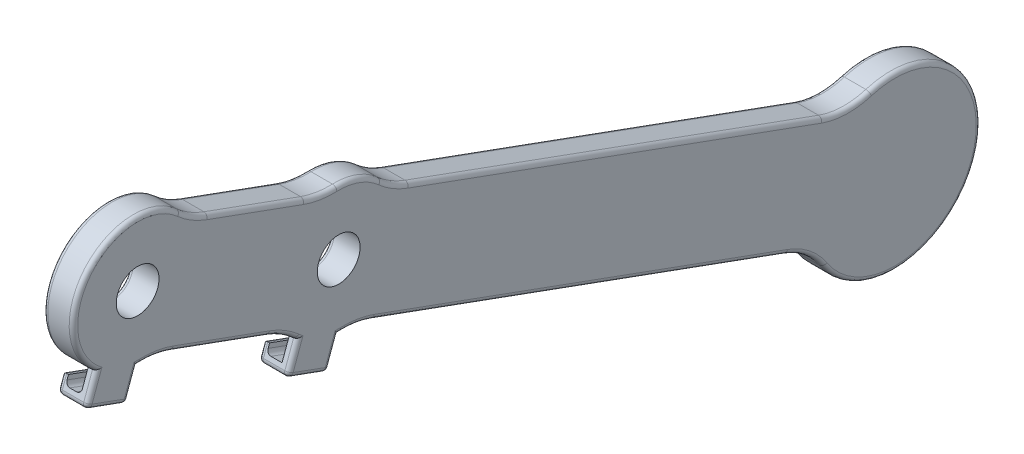
SolidWorks part; units mm, degrees
ref_plane "Front Plane" through (0, 0, 0) normal (1, 0, 0) x (0, 1, 0)
ref_plane "Top Plane" through (0, 0, 0) normal (0, 0, 1) x (0, 1, 0)
ref_plane "Right Plane" through (0, 0, 0) normal (0, 1, 0) x (-1, 0, 0)
sketch "Sketch1" plane through (0, 0, 0) normal (1, 0, 0) x (0, 1, 0)
  line L0 (-11.6048, -20) -> (24.9519, -20)
  line L1 (84.9519, 40) -> (84.9519, 57.8005)
  line L4 (-38.5328, 56.8878) -> (-47.7982, 43.6554)
  line L5 (64.9519, 37.5) -> (87.5414, -36.1119)
  line L6 (87.5414, -36.1119) -> (67.3498, -81.8536)
  line L7 (67.3498, -81.8536) -> (2.5345, -208.1983)
  line L8 (67.3498, -81.8536) -> (0, 0)
  line L9 (0, 0) -> (64.9519, 37.5) construction
  line L11 (-49.5322, 36.7009) -> (-46.3439, 10.7346)
  line L12 (-32.0778, 61.0001) -> (61.4789, 77.4967)
  arc A0 (24.9519, -20) -> (84.9519, 40) centre (24.9519, 40) ccw
  arc A1 (84.9519, 57.8005) -> (61.4789, 77.4967) centre (64.9519, 57.8005) ccw
  circle A3 centre (0, 0) radius 5
  circle A4 centre (0, 0) radius 10
  circle A5 centre (64.9519, 37.5) radius 5
  circle A6 centre (64.9519, 37.5) radius 10
  circle A7 centre (87.5414, -36.1119) radius 5
  circle A8 centre (87.5414, -36.1119) radius 10
  circle A9 centre (67.3498, -81.8536) radius 5
  circle A10 centre (67.3498, -81.8536) radius 10
  circle A11 centre (2.5345, -208.1983) radius 10
  circle A12 centre (2.5345, -208.1983) radius 50
  arc A13 (-46.3439, 10.7346) -> (-11.6048, -20) centre (-11.6048, 15) ccw
  arc A14 (-47.7982, 43.6554) -> (-49.5322, 36.7009) centre (-39.6067, 37.9196) ccw
  arc A16 (-32.0778, 61.0001) -> (-38.5328, 56.8878) centre (-30.3413, 51.152) ccw
  dimension "D3" = 60
  dimension "D16" = 20
  dimension "D17" = 10
  dimension "D18" = 20
  dimension "D19" = 100
  dimension "D22" = 35
  dimension "D24" = 10
  dimension "D7" = 10
  dimension "D1" = 20
  dimension "D4" = 20
  dimension "D5" = 95
  dimension "D9" = 10
  dimension "D10" = 75
  dimension "D11" = 77
  dimension "D12" = 50
  dimension "D13" = 142
  dimension "D14" = 3.34
  dimension "D15" = 30
  dimension "D20" = 106
sketch "Sketch3" plane through (0, 0, 0) normal (1, 0, 0) x (0, 1, 0)
  line L2 (94.8446, -52.5941) -> (86.6295, -75.1648)
  line L4 (77.7436, -99.5788) -> (42.5806, -196.1882)
  line L6 (87.5414, -36.1119) -> (70.4404, -83.0966) construction
  line L7 (70.4404, -83.0966) -> (23.139, -213.056) construction
  line L8 (71.3523, -44.0436) -> (63.1372, -66.6143)
  line L10 (54.2513, -91.0283) -> (19.0883, -187.6377)
  circle A3 centre (70.4404, -83.0966) radius 12.5 construction
  arc A8 (98.7258, -46.1073) -> (72.5487, -36.5796) centre (87.5414, -36.1119) ccw
  arc A9 (71.3523, -44.0436) -> (72.5487, -36.5796) centre (52.5584, -37.2032) ccw
  arc A10 (59.2559, -73.1011) -> (55.4477, -83.5643) centre (70.4404, -83.0966) ccw
  arc A11 (59.2559, -73.1011) -> (63.1372, -66.6143) centre (44.3433, -59.7739) ccw
  circle A12 centre (87.5414, -36.1119) radius 5
  arc A13 (98.9768, -41.1598) -> (76.106, -31.064) centre (87.5414, -36.1119) ccw construction
  circle A15 centre (70.4404, -83.0966) radius 5
  arc A16 (54.2513, -91.0283) -> (55.4477, -83.5643) centre (35.4574, -84.1879) ccw
  arc A18 (12.2082, -196.3074) -> (42.2783, -207.2521) centre (23.139, -213.056) ccw
  arc A19 (12.2082, -196.3074) -> (19.0883, -187.6377) centre (2.6437, -181.6524) ccw
  arc A20 (42.5806, -196.1882) -> (42.2783, -207.2521) centre (59.0252, -202.1736) ccw
  arc A21 (94.8446, -52.5941) -> (98.7258, -46.1073) centre (113.6384, -59.4345) cw
  circle A22 centre (23.139, -213.056) radius 12.5
  arc A23 (85.4331, -82.6288) -> (86.6295, -75.1648) centre (105.4234, -82.0052) cw
  arc A24 (77.7436, -99.5788) -> (81.6248, -93.092) centre (96.5374, -106.4192) cw
  arc A25 (81.6248, -93.092) -> (85.4331, -82.6288) centre (70.4404, -83.0966) ccw
  dimension "D2" = 35
  dimension "D3" = 20
  dimension "D4" = 10
  dimension "D5" = 25
  dimension "D6" = 10
  dimension "D7" = 25
  dimension "D12" = 30
  dimension "D13" = 20
  dimension "D8" = 138.3
  dimension "D9" = 0
  dimension "D10" = 50
  dimension "D11" = 110
extrude "Boss-Extrude3" add sketch "Sketch3" along normal blind 7
sketch "Sketch4" plane through (7, 0, 0) normal (1, 0, 0) x (0, 1, 0)
  line L0 (75.9622, -26.5766) -> (69.3844, -24.1824)
  line L1 (69.3844, -24.1824) -> (65.9642, -33.5793)
  line L2 (65.9642, -33.5793) -> (72.542, -35.9735)
  line L3 (67.6743, -28.8809) -> (87.5414, -36.1119) construction
  line L4 (87.5414, -36.1119) -> (70.4404, -83.0966) construction
  line L5 (52.2834, -71.1671) -> (58.8612, -73.5612)
  line L6 (52.2834, -71.1671) -> (48.8632, -80.564)
  line L7 (48.8632, -80.564) -> (55.441, -82.9581)
  line L8 (50.5733, -75.8655) -> (70.4404, -83.0966) construction
  line L9 (70.4404, -83.0966) -> (23.139, -213.056) construction
  arc A0 (98.7258, -46.1073) -> (72.5487, -36.5796) centre (87.5414, -36.1119) ccw construction
  arc A1 (75.9622, -26.5766) -> (72.542, -35.9735) centre (87.5414, -36.1119) ccw
  arc A2 (59.2559, -73.1011) -> (55.4477, -83.5643) centre (70.4404, -83.0966) ccw construction
  arc A3 (58.8612, -73.5612) -> (55.441, -82.9581) centre (70.4404, -83.0966) ccw
  dimension "D1" = 7
  dimension "D2" = 7
  dimension "D3" = 10
  dimension "D4" = 10
extrude "Boss-Extrude4" add sketch "Sketch4" against normal blind 2
sketch "Sketch5" plane through (5, 0, 0) normal (-1, 0, 0) x (0, -1, 0)
  line L0 (-69.3844, -24.1824) -> (-65.9642, -33.5793)
  line L1 (-69.3844, -24.1824) -> (-65.9642, -33.5793) construction
  line L2 (-65.9642, -33.5793) -> (-67.8436, -34.2634)
  line L3 (-65.9642, -33.5793) -> (-72.542, -35.9735) construction
  line L4 (-67.8436, -34.2634) -> (-71.2638, -24.8665)
  line L5 (-75.9622, -26.5766) -> (-69.3844, -24.1824) construction
  line L6 (-71.2638, -24.8665) -> (-69.3844, -24.1824)
  line L7 (-52.2834, -71.1671) -> (-54.1628, -71.8511)
  line L8 (-58.8612, -73.5612) -> (-52.2834, -71.1671) construction
  line L9 (-54.1628, -71.8511) -> (-50.7426, -81.248)
  line L10 (-48.8632, -80.564) -> (-55.441, -82.9581) construction
  line L11 (-50.7426, -81.248) -> (-48.8632, -80.564)
  line L12 (-48.8632, -80.564) -> (-52.2834, -71.1671)
  dimension "D1" = 2
  dimension "D2" = 2
extrude "Boss-Extrude5" add sketch "Sketch5" along normal up to surface (5 mm away) up to face at (0, 63.3182, -102.6645)
sketch "Sketch6" plane through (0, 70.9194, -25.8126) normal (0, 0.9397, -0.342) x (-1, 0, 0)
  line L0 (0, -48.9932) -> (0, -58.9932)
  line L1 (0, -58.9932) -> (-1.4, -58.9932)
  line L2 (0, -58.9932) -> (-5, -58.9932) construction
  line L3 (-1.4, -58.9932) -> (-1.4, -48.9932)
  line L4 (0, -48.9932) -> (-5, -48.9932) construction
  line L5 (-1.4, -48.9932) -> (0, -48.9932)
  dimension "D1" = 1.4
extrude "Boss-Extrude6" add sketch "Sketch6" along normal blind 2
sketch "Sketch7" plane through (0, 70.9194, -25.8126) normal (0, 0.9397, -0.342) x (-1, 0, 0)
  line L0 (0, 1.0068) -> (0, -8.9932)
  line L1 (0, -8.9932) -> (-1.4, -8.9932)
  line L2 (0, -8.9932) -> (-5, -8.9932) construction
  line L3 (-1.4, -8.9932) -> (-1.4, 1.0068)
  line L4 (0, 1.0068) -> (-5, 1.0068) construction
  line L5 (-1.4, 1.0068) -> (0, 1.0068)
  dimension "D1" = 1.4
extrude "Boss-Extrude7" add sketch "Sketch7" along normal blind 2
fillet "Fillet1" radius 1 58 edges at (0, 70.4404, -88.0966) (0, 23.139, -225.556) (0, 87.5414, -41.1119) (0, 67.2447, -55.329) (0, 61.5058, -70.0428) (0, 56.345, -77.9663) (0, 55.2053, -87.3533) (0, 36.6698, -139.333) (0, 16.3517, -192.5308) (0, 16.2986, -231.8499) (0, 41.5318, -201.6956) (0, 60.1621, -147.8835) (0, 79.3749, -96.1503) (0, 84.5358, -88.2269) (0, 85.6755, -78.8398) (0, 90.737, -63.8795) (0, 96.4759, -49.1657) (0, 92.6717, -22.0165) (0, 72.3063, -40.3687) (7, 97.3088, -24.7278) (7, 72.5423, -36.2766) (7, 96.4759, -49.1657) (7, 90.737, -63.8795) (7, 85.6755, -78.8398) (7, 84.5358, -88.2269) (7, 79.3749, -96.1503) (7, 60.1621, -147.8835) (7, 41.5318, -201.6956) (7, 16.2986, -231.8499) (7, 16.3517, -192.5308) (7, 36.6698, -139.333) (7, 55.2053, -87.3533) (7, 59.0563, -73.3292) (7, 55.4413, -83.2612) (7, 61.5058, -70.0428) (7, 67.2447, -55.329) (7, 72.3063, -40.3687) (7, 69.2531, -34.7764) (7, 67.6743, -28.8809) (7, 72.6733, -25.3795) (7, 52.1521, -81.7611) (7, 50.5733, -75.8655) (7, 55.5723, -72.3641) (0, 67.8436, -34.2634) (0, 71.4331, -30.249) (0, 71.2638, -24.8665) (3.5, 65.9642, -33.5793) (0, 67.6743, -28.8809) (3.5, 69.3844, -24.1824) (3.5, 48.8632, -80.564) (3.5, 52.2834, -71.1671) (0, 50.5733, -75.8655) (0, 50.7426, -81.248) (0, 54.332, -77.2336) (0, 54.1628, -71.8511) (1.4, 52.4527, -76.5496) (1.4, 69.5537, -29.5649) (5, 69.5537, -29.5649)
sketch "Sketch8" plane through (0, 0, 0) normal (-1, 0, 0) x (0, -1, 0)
  circle A0 centre (-23.139, -213.056) radius 15
  dimension "D1" = 30
extrude "Boss-Extrude8" add sketch "Sketch8" against normal blind 7
